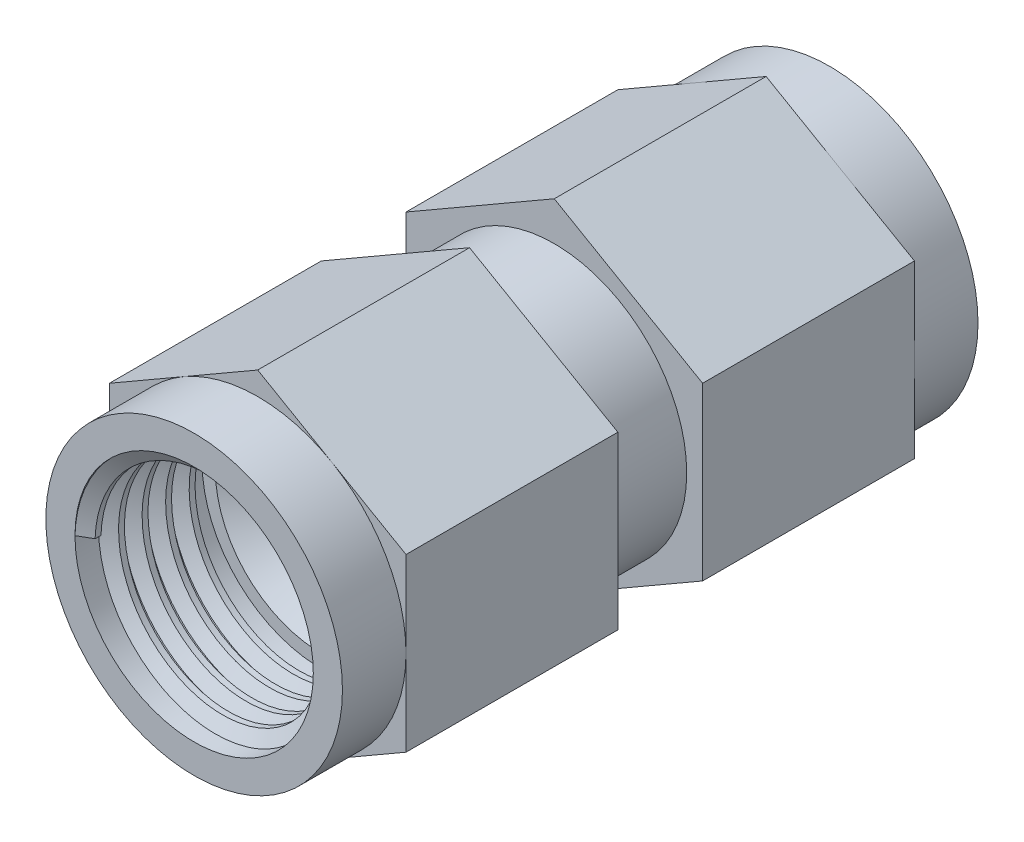
SolidWorks part; units mm, degrees
material "6061-T6 (SS)"
ref_plane "Front Plane" through (0, 0, 0) normal (0, 0, 1) x (1, 0, 0)
ref_plane "Top Plane" through (0, 0, 0) normal (0, 1, 0) x (1, 0, 0)
ref_plane "Right Plane" through (0, 0, 0) normal (1, 0, 0) x (0, 0, -1)
sketch "Sketch4" plane through (0, 0, 0) normal (0, 0, 1) x (1, 0, 0)
  line L1 (0, 10.2653) -> (-8.89, 5.1326)
  line L2 (-8.89, 5.1326) -> (-8.89, -5.1326)
  line L3 (-8.89, -5.1326) -> (0, -10.2653)
  line L4 (0, -10.2653) -> (8.89, -5.1326)
  line L5 (8.89, -5.1326) -> (8.89, 5.1326)
  line L6 (8.89, 5.1326) -> (0, 10.2653)
  circle A0 centre (0, 0) radius 8.89 construction
  circle A1 centre (0, 0) radius 3.81
  dimension "D1" = 17.78
  dimension "D2" = 7.62
extrude "Boss-Extrude3" add sketch "Sketch4" along normal blind 38.1
sketch "Sketch6" plane through (0, 0, 38.1) normal (0, 0, 1) x (1, 0, 0)
  circle A0 centre (0, 0) radius 7.1438
  dimension "D1" = 14.2875
extrude "Cut-Extrude1" cut sketch "Sketch6" against normal blind 7.62
sketch "Sketch7" plane through (0, 0, 0) normal (0, 0, -1) x (-1, 0, 0)
  circle A0 centre (0, 0) radius 7.1438
  dimension "D1" = 14.2875
extrude "Cut-Extrude2" cut sketch "Sketch7" against normal blind 7.62
sketch "Sketch8" plane through (0, 0, 38.1) normal (0, 0, 1) x (1, 0, 0)
  circle A2 centre (0, 0) radius 8.89
  circle A3 centre (0, 0) radius 11.43
  dimension "D1" = 17.78
  dimension "D2" = 22.86
extrude "Cut-Extrude7" cut sketch "Sketch8" against normal blind 3.81
ref_plane "Plane1" through (0, 0, 19.05) normal (0, 0, 1) x (1, 0, 0)
sketch "Sketch10" plane through (0, 0, 19.05) normal (0, 0, 1) x (1, 0, 0)
  circle A0 centre (0, 0) radius 3.81
  circle A1 centre (0, 0) radius 7.9375
  dimension "D1" = 15.875
  dimension "D2" = 7.62
extrude "Cut-Extrude6" cut sketch "Sketch10" against normal mid plane 5.08 flip side to cut
chamfer "Chamfer2" distance 2.54 angle 37 2 edges at (-3.81, 0, 7.62) (3.81, 0, 30.48) first distance on face at (-3.81, 0, 7.62) first distance on face at (3.81, 0, 30.48)
mirror "Mirror2" about plane through (0, 0, 19.05) normal (0, 0, 1) of "Cut-Extrude7"
thread "Thread1" pitch 1.4111 method extrude profile "Thread Profile7" start angle 0, offset 0, length 6.35, pitch 1.4111, diameter 14.2875
ref_plane "Plane8" through (-7.1438, 0, 38.1) normal (0, -1, 0) x (-1, 0, 0)
sketch "Thread Profile7" plane through (-7.1438, 0, 38.1) normal (0, -1, 0) x (-1, 0, 0)
  line L0 (0, 0) -> (0, 1.4111) construction
  line L11 (0, 0) -> (0, 1.2347)
  line L12 (0, 1.2347) -> (-0.7638, 0.7937)
  line L13 (-0.7638, 0.7937) -> (-0.7638, 0.441)
  line L15 (-0.7638, 0.441) -> (0, 0)
  line L17 (-0.7638, 0.6174) -> (0, 0.6174) construction
  point P2 (0, 0)
  dimension "Pitch" = 1.4111
  dimension "Profile_Angle" = 60
  dimension "Profile_Land" = 0.3528
  dimension "Profile_Height" = 0.7638
thread "Thread2" pitch 1.4111 method extrude profile "Thread Profile8" start angle 0, offset 0, length 6.35, pitch 1.4111, diameter 14.2875
ref_plane "Plane9" through (7.1438, 0, 0) normal (0, -1, 0) x (1, 0, 0)
sketch "Thread Profile8" plane through (7.1438, 0, 0) normal (0, -1, 0) x (1, 0, 0)
  line L0 (0, 0) -> (0, 1.4111) construction
  line L11 (0, 0) -> (0, 1.2347)
  line L12 (0, 1.2347) -> (-0.7638, 0.7937)
  line L13 (-0.7638, 0.7937) -> (-0.7638, 0.441)
  line L15 (-0.7638, 0.441) -> (0, 0)
  line L17 (-0.7638, 0.6174) -> (0, 0.6174) construction
  point P2 (0, 0)
  dimension "Pitch" = 1.4111
  dimension "Profile_Angle" = 60
  dimension "Profile_Land" = 0.3528
  dimension "Profile_Height" = 0.7638
